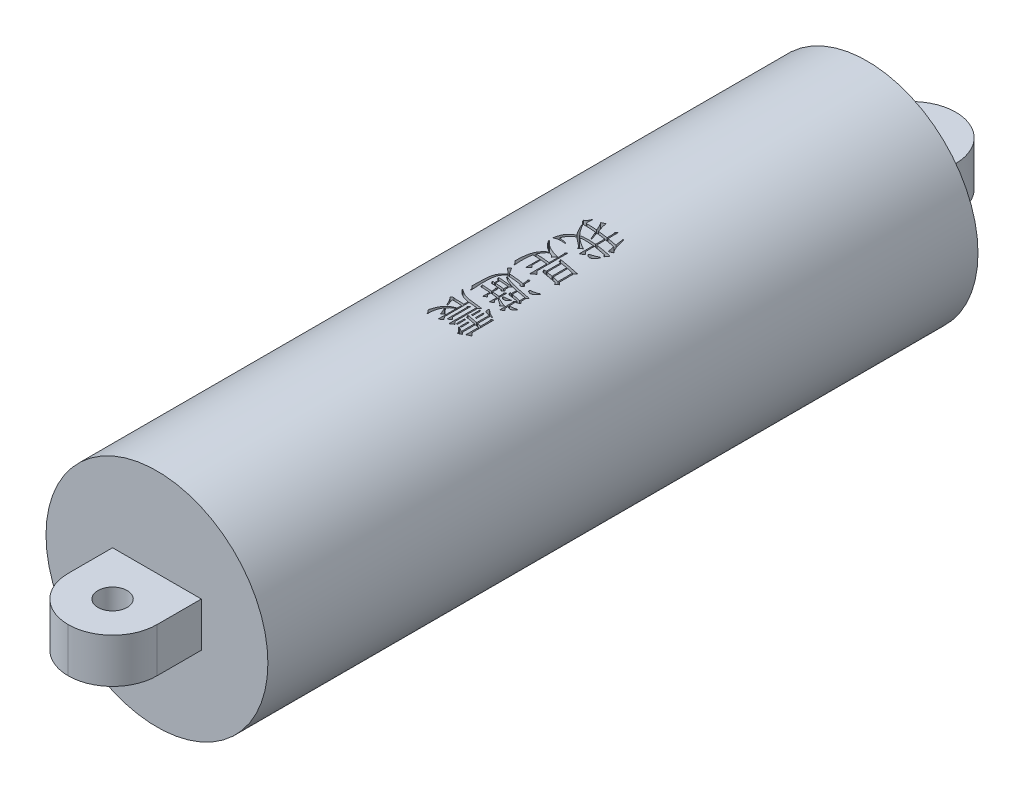
SolidWorks part; units mm, degrees
ref_plane "前视基准面" through (0, 0, 0) normal (0, 0, 1) x (1, 0, 0)
ref_plane "上视基准面" through (0, 0, 0) normal (0, 1, 0) x (1, 0, 0)
ref_plane "右视基准面" through (0, 0, 0) normal (1, 0, 0) x (0, 0, -1)
sketch "草图1" plane through (0, 0, 0) normal (0, 0, 1) x (1, 0, 0)
  circle A0 centre (0, 0) radius 12.5
  dimension "D1" = 25
extrude "凸台-拉伸1" add sketch "草图1" along normal blind 80
sketch "草图2" plane through (0, 0, 80) normal (0, 0, 1) x (1, 0, 0)
  line L1 (-5, 2.5) -> (5, 2.5)
  line L2 (-5, 2.5) -> (-5, -2.5)
  line L3 (-5, -2.5) -> (5, -2.5)
  line L4 (5, 2.5) -> (5, -2.5)
  line L5 (-5, 2.5) -> (5, -2.5) construction
  line L6 (-5, -2.5) -> (5, 2.5) construction
  point P0 (0, 0)
  dimension "D1" = 10
  dimension "D2" = 5
extrude "凸台-拉伸2" add sketch "草图2" along normal blind 10
extrude "凸台-拉伸3" add sketch "草图2<2>" against normal blind 10 from surface starting at face at (12.5, 0, 0)
sketch "草图2<2>" plane through (0, 0, 80) normal (0, 0, 1) x (1, 0, 0) same geometry as "草图2"
sketch "草图4" plane through (0, -2.5, 0) normal (0, -1, 0) x (1, 0, 0)
  line L0 (0, 90) -> (0, -10) construction
  line L1 (-5, 90) -> (5, 90) construction
  line L2 (-5, -10) -> (5, -10) construction
  line L3 (-5, 85) -> (5, 85) construction
  line L4 (-5, 90) -> (-5, 80) construction
  line L5 (5, 90) -> (5, 80) construction
  line L6 (-12.5, 40) -> (12.5, 40) construction
  line L7 (-12.5, 80) -> (-12.5, 0) construction
  line L8 (12.5, 0) -> (12.5, 80) construction
  circle A0 centre (0, 85) radius 1.65
  circle A1 centre (0, -5) radius 1.65
  dimension "D1" = 3.3
extrude "切除-拉伸1" cut sketch "草图4" against normal through all
fillet "圆角1" radius 5 4 edges at (-5, 0, -10) (5, 0, -10) (5, 0, 90) (-5, 0, 90)
sketch "草图5" plane through (0, 2.5, 0) normal (0, 1, 0) x (1, 0, 0)
  line L0 (0, 5) -> (0, -85) construction
  text T0 "我是避震"
extrude "切除-拉伸2" cut sketch "草图5" against normal through all and the other way through all
